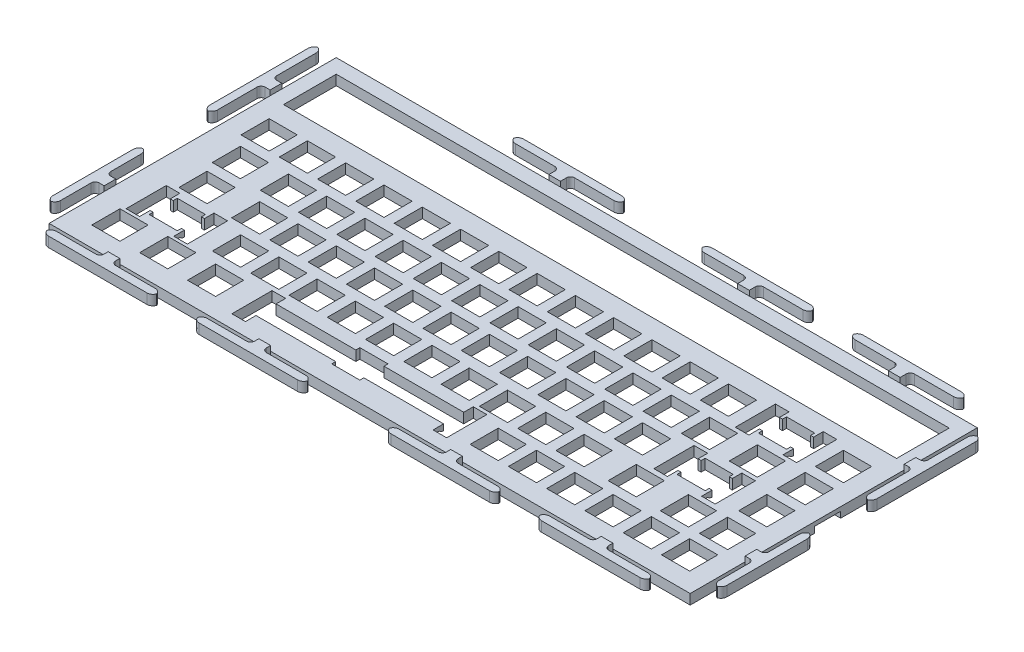
SolidWorks part; units mm, degrees
ref_plane "Front Plane" through (0, 0, 0) normal (0, 0, 1) x (1, 0, 0)
ref_plane "Top Plane" through (0, 0, 0) normal (0, 1, 0) x (1, 0, 0)
ref_plane "Right Plane" through (0, 0, 0) normal (1, 0, 0) x (0, 0, -1)
sketch "Sketch1" plane through (0, 0, 0) normal (0, 1, 0) x (1, 0, 0)
  line L2 (-75.7545, 37.9956) -> (-61.7545, 37.9956)
  line L3 (-94.8265, 37.9956) -> (-80.8265, 37.9956)
  line L4 (-94.8265, 37.9956) -> (-94.8265, 51.9956)
  line L5 (-94.8265, 51.9956) -> (-80.8265, 51.9956)
  line L6 (-80.8265, 37.9956) -> (-80.8265, 51.9956)
  line L7 (-75.7545, 37.9956) -> (-75.7545, 51.9956)
  line L8 (-75.7545, 51.9956) -> (-61.7545, 51.9956)
  line L9 (-61.7545, 37.9956) -> (-61.7545, 51.9956)
  line L10 (133.7495, 37.9956) -> (147.7495, 37.9956)
  line L11 (-37.6545, 37.9956) -> (-23.6545, 37.9956)
  line L12 (-56.7045, 37.9956) -> (-42.7045, 37.9956)
  line L13 (-56.7045, 37.9956) -> (-56.7045, 51.9956)
  line L14 (-56.7045, 51.9956) -> (-42.7045, 51.9956)
  line L15 (-42.7045, 37.9956) -> (-42.7045, 51.9956)
  line L16 (-37.6545, 37.9956) -> (-37.6545, 51.9956)
  line L17 (-37.6545, 51.9956) -> (-23.6545, 51.9956)
  line L18 (-23.6545, 37.9956) -> (-23.6545, 51.9956)
  line L19 (133.7495, 37.9956) -> (133.7495, 51.9956)
  line L20 (133.7495, 51.9956) -> (147.7495, 51.9956)
  line L21 (0.4455, 37.9956) -> (14.4455, 37.9956)
  line L22 (-18.6045, 37.9956) -> (-4.6045, 37.9956)
  line L23 (-18.6045, 37.9956) -> (-18.6045, 51.9956)
  line L24 (-18.6045, 51.9956) -> (-4.6045, 51.9956)
  line L25 (-4.6045, 37.9956) -> (-4.6045, 51.9956)
  line L26 (0.4455, 37.9956) -> (0.4455, 51.9956)
  line L27 (0.4455, 51.9956) -> (14.4455, 51.9956)
  line L28 (14.4455, 37.9956) -> (14.4455, 51.9956)
  line L29 (147.7495, 37.9956) -> (147.7495, 51.9956)
  line L30 (38.5455, 37.9956) -> (52.5455, 37.9956)
  line L31 (19.4955, 37.9956) -> (33.4955, 37.9956)
  line L32 (19.4955, 37.9956) -> (19.4955, 51.9956)
  line L33 (19.4955, 51.9956) -> (33.4955, 51.9956)
  line L34 (33.4955, 37.9956) -> (33.4955, 51.9956)
  line L35 (38.5455, 37.9956) -> (38.5455, 51.9956)
  line L36 (38.5455, 51.9956) -> (52.5455, 51.9956)
  line L37 (52.5455, 37.9956) -> (52.5455, 51.9956)
  line L38 (147.7495, 44.9956) -> (154.1495, 44.9956) construction
  line L39 (167.1835, 18.9456) -> (181.1835, 18.9456)
  line L40 (167.1835, 18.9456) -> (167.1835, 32.9456)
  line L41 (76.6455, 37.9956) -> (90.6455, 37.9956)
  line L42 (57.5955, 37.9956) -> (71.5955, 37.9956)
  line L43 (57.5955, 37.9956) -> (57.5955, 51.9956)
  line L44 (57.5955, 51.9956) -> (71.5955, 51.9956)
  line L45 (71.5955, 37.9956) -> (71.5955, 51.9956)
  line L46 (76.6455, 37.9956) -> (76.6455, 51.9956)
  line L47 (76.6455, 51.9956) -> (90.6455, 51.9956)
  line L48 (90.6455, 37.9956) -> (90.6455, 51.9956)
  line L49 (167.1835, 32.9456) -> (181.1835, 32.9456)
  line L50 (114.7225, 37.9956) -> (128.7225, 37.9956)
  line L51 (95.6955, 37.9956) -> (109.6955, 37.9956)
  line L52 (95.6955, 37.9956) -> (95.6955, 51.9956)
  line L53 (95.6955, 51.9956) -> (109.6955, 51.9956)
  line L54 (109.6955, 37.9956) -> (109.6955, 51.9956)
  line L55 (114.7225, 37.9956) -> (114.7225, 51.9956)
  line L56 (114.7225, 51.9956) -> (128.7225, 51.9956)
  line L57 (128.7225, 37.9956) -> (128.7225, 51.9956)
  line L58 (181.1835, 18.9456) -> (181.1835, 32.9456)
  line L59 (157.3735, 25.9456) -> (167.1835, 25.9456) construction
  line L73 (162.3995, 52.2456) -> (176.3995, 52.2456)
  line L75 (176.3995, 38.2456) -> (162.3995, 38.2456)
  line L77 (176.3995, 52.2456) -> (176.3995, 50.2456)
  line L78 (176.3995, 50.2456) -> (177.8995, 50.2456)
  line L79 (177.8995, 50.2456) -> (177.8995, 54.9956)
  line L80 (177.8995, 54.9956) -> (184.6495, 54.9956)
  line L81 (184.6495, 54.9956) -> (184.6495, 34.9956)
  line L82 (184.6495, 34.9956) -> (177.8995, 34.9956)
  line L83 (177.8995, 34.9956) -> (177.8995, 40.2456)
  line L84 (177.8995, 40.2456) -> (176.3995, 40.2456)
  line L85 (176.3995, 40.2456) -> (176.3995, 38.2456)
  line L86 (162.3995, 52.2456) -> (162.3995, 50.2456)
  line L87 (160.8995, 54.9956) -> (160.8995, 50.2456)
  line L88 (160.8995, 50.2456) -> (162.3995, 50.2456)
  line L89 (160.8995, 54.9956) -> (154.1495, 54.9956)
  line L90 (154.1495, 54.9956) -> (154.1495, 34.9956)
  line L91 (154.1495, 34.9956) -> (160.8995, 34.9956)
  line L92 (160.8995, 34.9956) -> (160.8995, 40.2456)
  line L93 (160.8995, 40.2456) -> (162.3995, 40.2456)
  line L94 (162.3995, 40.2456) -> (162.3995, 38.2456)
  line L116 (-47.1265, 18.9456) -> (-33.1265, 18.9456)
  line L117 (-66.1765, 18.9456) -> (-52.1765, 18.9456)
  line L118 (-66.1765, 18.9456) -> (-66.1765, 32.9456)
  line L119 (-66.1765, 32.9456) -> (-52.1765, 32.9456)
  line L120 (-52.1765, 18.9456) -> (-52.1765, 32.9456)
  line L121 (-47.1265, 18.9456) -> (-47.1265, 32.9456)
  line L122 (-47.1265, 32.9456) -> (-33.1265, 32.9456)
  line L123 (-33.1265, 18.9456) -> (-33.1265, 32.9456)
  line L125 (-9.0515, 18.9456) -> (4.9485, 18.9456)
  line L126 (-28.0765, 18.9456) -> (-14.0765, 18.9456)
  line L127 (-28.0765, 18.9456) -> (-28.0765, 32.9456)
  line L128 (-28.0765, 32.9456) -> (-14.0765, 32.9456)
  line L129 (-14.0765, 18.9456) -> (-14.0765, 32.9456)
  line L130 (-9.0515, 18.9456) -> (-9.0515, 32.9456)
  line L131 (-9.0515, 32.9456) -> (4.9485, 32.9456)
  line L132 (4.9485, 18.9456) -> (4.9485, 32.9456)
  line L135 (29.0735, 18.9456) -> (43.0735, 18.9456)
  line L136 (9.9485, 18.9456) -> (23.9485, 18.9456)
  line L137 (9.9485, 18.9456) -> (9.9485, 32.9456)
  line L138 (9.9485, 32.9456) -> (23.9485, 32.9456)
  line L139 (23.9485, 18.9456) -> (23.9485, 32.9456)
  line L140 (29.0735, 18.9456) -> (29.0735, 32.9456)
  line L141 (29.0735, 32.9456) -> (43.0735, 32.9456)
  line L142 (43.0735, 18.9456) -> (43.0735, 32.9456)
  line L144 (67.1485, 18.9456) -> (81.1485, 18.9456)
  line L145 (48.1235, 18.9456) -> (62.1235, 18.9456)
  line L146 (48.1235, 18.9456) -> (48.1235, 32.9456)
  line L147 (48.1235, 32.9456) -> (62.1235, 32.9456)
  line L148 (62.1235, 18.9456) -> (62.1235, 32.9456)
  line L149 (67.1485, 18.9456) -> (67.1485, 32.9456)
  line L150 (67.1485, 32.9456) -> (81.1485, 32.9456)
  line L151 (81.1485, 18.9456) -> (81.1485, 32.9456)
  line L152 (159.9865, 14.1456) -> (173.9865, 14.1456)
  line L153 (-42.3635, -0.1044) -> (-28.3635, -0.1044)
  line L154 (-61.4135, -0.1044) -> (-47.4135, -0.1044)
  line L155 (105.2735, 18.9456) -> (119.2735, 18.9456)
  line L156 (86.2235, 18.9456) -> (100.2235, 18.9456)
  line L157 (86.2235, 18.9456) -> (86.2235, 32.9456)
  line L158 (86.2235, 32.9456) -> (100.2235, 32.9456)
  line L159 (100.2235, 18.9456) -> (100.2235, 32.9456)
  line L160 (105.2735, 18.9456) -> (105.2735, 32.9456)
  line L161 (105.2735, 32.9456) -> (119.2735, 32.9456)
  line L162 (119.2735, 18.9456) -> (119.2735, 32.9456)
  line L163 (-61.4135, -0.1044) -> (-61.4135, 13.8956)
  line L172 (-94.8265, 37.9956) -> (-94.8265, 32.9456) construction
  line L173 (-61.4135, 13.8956) -> (-47.4135, 13.8956)
  line L174 (-47.4135, -0.1044) -> (-47.4135, 13.8956)
  line L175 (-90.0635, 18.9456) -> (-76.0635, 18.9456)
  line L176 (-90.0635, 18.9456) -> (-90.0635, 32.9456)
  line L177 (-90.0635, 32.9456) -> (-76.0635, 32.9456)
  line L178 (-76.0635, 18.9456) -> (-76.0635, 32.9456)
  line L179 (-94.8265, 32.9456) -> (-90.0635, 32.9456) construction
  line L180 (124.3235, 18.9456) -> (138.3235, 18.9456)
  line L185 (124.3235, 18.9456) -> (124.3235, 32.9456)
  line L186 (124.3235, 32.9456) -> (138.3235, 32.9456)
  line L187 (138.3235, 18.9456) -> (138.3235, 32.9456)
  line L188 (-42.3635, -0.1044) -> (-42.3635, 13.8956)
  line L189 (143.3735, 18.9456) -> (157.3735, 18.9456)
  line L190 (143.3735, 18.9456) -> (143.3735, 32.9456)
  line L191 (143.3735, 32.9456) -> (157.3735, 32.9456)
  line L192 (157.3735, 18.9456) -> (157.3735, 32.9456)
  line L193 (-42.3635, 13.8956) -> (-28.3635, 13.8956)
  line L194 (-28.3635, -0.1044) -> (-28.3635, 13.8956)
  line L195 (-4.2635, -0.1044) -> (9.7365, -0.1044)
  line L196 (-23.3135, -0.1044) -> (-9.3135, -0.1044)
  line L197 (-23.3135, -0.1044) -> (-23.3135, 13.8956)
  line L198 (-23.3135, 13.8956) -> (-9.3135, 13.8956)
  line L199 (-9.3135, -0.1044) -> (-9.3135, 13.8956)
  line L200 (-4.2635, -0.1044) -> (-4.2635, 13.8956)
  line L201 (-4.2635, 13.8956) -> (9.7365, 13.8956)
  line L202 (9.7365, -0.1044) -> (9.7365, 13.8956)
  line L203 (33.8365, -0.1044) -> (47.8365, -0.1044)
  line L204 (14.7865, -0.1044) -> (28.7865, -0.1044)
  line L205 (14.7865, -0.1044) -> (14.7865, 13.8956)
  line L206 (14.7865, 13.8956) -> (28.7865, 13.8956)
  line L207 (28.7865, -0.1044) -> (28.7865, 13.8956)
  line L208 (33.8365, -0.1044) -> (33.8365, 13.8956)
  line L209 (33.8365, 13.8956) -> (47.8365, 13.8956)
  line L210 (47.8365, -0.1044) -> (47.8365, 13.8956)
  line L211 (71.9365, -0.1044) -> (85.9365, -0.1044)
  line L212 (52.8865, -0.1044) -> (66.8865, -0.1044)
  line L213 (52.8865, -0.1044) -> (52.8865, 13.8956)
  line L214 (52.8865, 13.8956) -> (66.8865, 13.8956)
  line L215 (66.8865, -0.1044) -> (66.8865, 13.8956)
  line L216 (71.9365, -0.1044) -> (71.9365, 13.8956)
  line L217 (71.9365, 13.8956) -> (85.9365, 13.8956)
  line L218 (85.9365, -0.1044) -> (85.9365, 13.8956)
  line L219 (110.0365, -0.1044) -> (124.0365, -0.1044)
  line L220 (90.9865, -0.1044) -> (104.9865, -0.1044)
  line L221 (90.9865, -0.1044) -> (90.9865, 13.8956)
  line L222 (90.9865, 13.8956) -> (104.9865, 13.8956)
  line L223 (104.9865, -0.1044) -> (104.9865, 13.8956)
  line L224 (110.0365, -0.1044) -> (110.0365, 13.8956)
  line L225 (110.0365, 13.8956) -> (124.0365, 13.8956)
  line L226 (124.0365, -0.1044) -> (124.0365, 13.8956)
  line L227 (-87.6075, -0.1044) -> (-73.6075, -0.1044)
  line L228 (-87.6075, -0.1044) -> (-87.6075, 13.8956)
  line L229 (-87.6075, 13.8956) -> (-73.6075, 13.8956)
  line L230 (-73.6075, -0.1044) -> (-73.6075, 13.8956)
  line L231 (-90.0635, 18.9456) -> (-90.0635, 13.8956) construction
  line L232 (129.0865, -0.1044) -> (143.0865, -0.1044)
  line L233 (129.0865, -0.1044) -> (129.0865, 13.8956)
  line L234 (129.0865, 13.8956) -> (143.0865, 13.8956)
  line L235 (143.0865, -0.1044) -> (143.0865, 13.8956)
  line L240 (-90.0635, 13.8956) -> (-87.6075, 13.8956) construction
  line L241 (173.9865, 0.1456) -> (159.9865, 0.1456)
  line L242 (173.9865, 14.1456) -> (173.9865, 12.1456)
  line L243 (173.9865, 12.1456) -> (175.4865, 12.1456)
  line L244 (175.4865, 12.1456) -> (175.4865, 16.8956)
  line L245 (175.4865, 16.8956) -> (182.2365, 16.8956)
  line L246 (182.2365, 16.8956) -> (182.2365, -3.1044)
  line L247 (182.2365, -3.1044) -> (175.4865, -3.1044)
  line L248 (175.4865, -3.1044) -> (175.4865, 2.1456)
  line L249 (175.4865, 2.1456) -> (173.9865, 2.1456)
  line L250 (173.9865, 2.1456) -> (173.9865, 0.1456)
  line L251 (159.9865, 14.1456) -> (159.9865, 12.1456)
  line L252 (158.4865, 16.8956) -> (158.4865, 12.1456)
  line L253 (158.4865, 12.1456) -> (159.9865, 12.1456)
  line L254 (158.4865, 16.8956) -> (151.7365, 16.8956)
  line L255 (151.7365, 16.8956) -> (151.7365, -3.1044)
  line L256 (151.7365, -3.1044) -> (158.4865, -3.1044)
  line L257 (158.4865, -3.1044) -> (158.4865, 2.1456)
  line L258 (158.4865, 2.1456) -> (159.9865, 2.1456)
  line L259 (159.9865, 2.1456) -> (159.9865, 0.1456)
  line L260 (143.0865, 12.1456) -> (151.7365, 12.1456) construction
  line L262 (-32.8385, -19.1544) -> (-18.8385, -19.1544)
  line L263 (-51.8885, -19.1544) -> (-37.8885, -19.1544)
  line L264 (-51.8885, -19.1544) -> (-51.8885, -5.1544)
  line L265 (-51.8885, -5.1544) -> (-37.8885, -5.1544)
  line L266 (-37.8885, -19.1544) -> (-37.8885, -5.1544)
  line L267 (-32.8385, -19.1544) -> (-32.8385, -5.1544)
  line L268 (-32.8385, -5.1544) -> (-18.8385, -5.1544)
  line L269 (-18.8385, -19.1544) -> (-18.8385, -5.1544)
  line L270 (5.2615, -19.1544) -> (19.2615, -19.1544)
  line L271 (-13.7885, -19.1544) -> (0.2115, -19.1544)
  line L272 (-13.7885, -19.1544) -> (-13.7885, -5.1544)
  line L273 (-13.7885, -5.1544) -> (0.2115, -5.1544)
  line L274 (0.2115, -19.1544) -> (0.2115, -5.1544)
  line L275 (5.2615, -19.1544) -> (5.2615, -5.1544)
  line L276 (5.2615, -5.1544) -> (19.2615, -5.1544)
  line L277 (19.2615, -19.1544) -> (19.2615, -5.1544)
  line L278 (43.3615, -19.1544) -> (57.3615, -19.1544)
  line L279 (24.3115, -19.1544) -> (38.3115, -19.1544)
  line L280 (24.3115, -19.1544) -> (24.3115, -5.1544)
  line L281 (24.3115, -5.1544) -> (38.3115, -5.1544)
  line L282 (38.3115, -19.1544) -> (38.3115, -5.1544)
  line L283 (43.3615, -19.1544) -> (43.3615, -5.1544)
  line L284 (43.3615, -5.1544) -> (57.3615, -5.1544)
  line L285 (57.3615, -19.1544) -> (57.3615, -5.1544)
  line L286 (81.4615, -19.6544) -> (95.4615, -19.6544)
  line L287 (62.4115, -19.6544) -> (76.4115, -19.6544)
  line L288 (62.4115, -19.6544) -> (62.4115, -5.6544)
  line L289 (62.4115, -5.6544) -> (76.4115, -5.6544)
  line L290 (76.4115, -19.6544) -> (76.4115, -5.6544)
  line L291 (81.4615, -19.6544) -> (81.4615, -5.6544)
  line L292 (81.4615, -5.6544) -> (95.4615, -5.6544)
  line L293 (95.4615, -19.6544) -> (95.4615, -5.6544)
  line L294 (119.5615, -19.6544) -> (133.5615, -19.6544)
  line L295 (100.5115, -19.6544) -> (114.5115, -19.6544)
  line L296 (100.5115, -19.6544) -> (100.5115, -5.6544)
  line L297 (100.5115, -5.6544) -> (114.5115, -5.6544)
  line L298 (114.5115, -19.6544) -> (114.5115, -5.6544)
  line L299 (119.5615, -19.6544) -> (119.5615, -5.6544)
  line L300 (119.5615, -5.6544) -> (133.5615, -5.6544)
  line L301 (133.5615, -19.6544) -> (133.5615, -5.6544)
  line L306 (-83.3445, -5.1544) -> (-69.3445, -5.1544)
  line L307 (145.5235, -19.6544) -> (159.5235, -19.6544)
  line L308 (145.5235, -19.6544) -> (145.5235, -5.6544)
  line L309 (145.5235, -5.6544) -> (159.5235, -5.6544)
  line L310 (159.5235, -19.6544) -> (159.5235, -5.6544)
  line L311 (-69.3445, -19.1544) -> (-83.3445, -19.1544)
  line L331 (171.4855, -19.6544) -> (185.4855, -19.6544)
  line L332 (171.4855, -19.6544) -> (171.4855, -5.6544)
  line L333 (171.4855, -5.6544) -> (185.4855, -5.6544)
  line L334 (185.4855, -19.6544) -> (185.4855, -5.6544)
  line L335 (159.5235, -12.6544) -> (171.4855, -12.6544) construction
  line L336 (-61.4135, -0.1044) -> (-61.4135, -5.1544) construction
  line L337 (-61.4135, -5.1544) -> (-51.8885, -5.1544) construction
  line L338 (-104.4215, 94.9896) -> (-117.5239, 94.9896) construction
  line L339 (-97.2765, 61.6456) -> (207.7235, 61.6456)
  line L340 (190.9955, 18.9456) -> (204.9955, 18.9456)
  line L341 (190.9955, 18.9456) -> (190.9955, 32.9456)
  line L342 (190.9955, 32.9456) -> (204.9955, 32.9456)
  line L343 (204.9955, 18.9456) -> (204.9955, 32.9456)
  line L344 (181.1835, 25.9456) -> (190.9955, 25.9456) construction
  line L345 (190.9745, 37.9956) -> (204.9745, 37.9956)
  line L346 (190.9745, 37.9956) -> (190.9745, 51.9956)
  line L347 (190.9745, 51.9956) -> (204.9745, 51.9956)
  line L348 (204.9745, 37.9956) -> (204.9745, 51.9956)
  line L349 (184.6495, 44.9956) -> (190.9745, 44.9956) construction
  line L350 (190.9425, -0.1044) -> (204.9425, -0.1044)
  line L351 (190.9425, -0.1044) -> (190.9425, 13.8956)
  line L352 (190.9425, 13.8956) -> (204.9425, 13.8956)
  line L353 (204.9425, -0.1044) -> (204.9425, 13.8956)
  line L354 (182.2365, 6.8956) -> (190.9425, 6.8956) construction
  line L355 (190.9855, -19.6544) -> (204.9855, -19.6544)
  line L356 (190.9855, -19.6544) -> (190.9855, -5.6544)
  line L357 (190.9855, -5.6544) -> (204.9855, -5.6544)
  line L358 (204.9855, -19.6544) -> (204.9855, -5.6544)
  line L359 (185.4855, -12.6544) -> (190.9855, -12.6544) construction
  line L360 (-69.3445, -5.1544) -> (-69.3445, -7.1544)
  line L361 (-69.3445, -7.1544) -> (-67.8445, -7.1544)
  line L362 (-67.8445, -7.1544) -> (-67.8445, -2.4044)
  line L363 (-67.8445, -2.4044) -> (-61.0945, -2.4044)
  line L364 (-61.0945, -2.4044) -> (-61.0945, -22.4044)
  line L365 (-61.0945, -22.4044) -> (-67.8445, -22.4044)
  line L366 (-67.8445, -22.4044) -> (-67.8445, -17.1544)
  line L367 (-67.8445, -17.1544) -> (-69.3445, -17.1544)
  line L368 (-69.3445, -17.1544) -> (-69.3445, -19.1544)
  line L369 (-83.3445, -5.1544) -> (-83.3445, -7.1544)
  line L370 (-84.8445, -2.4044) -> (-84.8445, -7.1544)
  line L371 (-84.8445, -7.1544) -> (-83.3445, -7.1544)
  line L372 (-84.8445, -2.4044) -> (-91.5945, -2.4044)
  line L373 (-91.5945, -2.4044) -> (-91.5945, -22.4044)
  line L374 (-91.5945, -22.4044) -> (-84.8445, -22.4044)
  line L375 (-84.8445, -22.4044) -> (-84.8445, -17.1544)
  line L376 (-84.8445, -17.1544) -> (-83.3445, -17.1544)
  line L377 (-83.3445, -17.1544) -> (-83.3445, -19.1544)
  line L378 (-93.0945, -37.9544) -> (-79.0945, -37.9544)
  line L379 (-93.0945, -37.9544) -> (-93.0945, -23.9544)
  line L380 (-93.0945, -23.9544) -> (-79.0945, -23.9544)
  line L381 (-79.0945, -37.9544) -> (-79.0945, -23.9544)
  line L382 (-69.2945, -37.9544) -> (-55.2945, -37.9544)
  line L383 (-69.2945, -37.9544) -> (-69.2945, -23.9544)
  line L384 (-69.2945, -23.9544) -> (-55.2945, -23.9544)
  line L385 (-55.2945, -37.9544) -> (-55.2945, -23.9544)
  line L390 (-45.4945, -37.9544) -> (-31.4945, -37.9544)
  line L391 (-45.4945, -37.9544) -> (-45.4945, -23.9544)
  line L392 (-45.4945, -23.9544) -> (-31.4945, -23.9544)
  line L393 (-31.4945, -37.9544) -> (-31.4945, -23.9544)
  line L394 (-55.2945, -23.9544) -> (-45.4945, -23.9544) construction
  line L395 (26.4395, -24.1144) -> (40.4395, -24.1144)
  line L396 (40.4395, -38.1144) -> (26.4395, -38.1144)
  line L397 (40.4395, -24.1144) -> (40.4395, -26.1144)
  line L398 (40.4395, -26.1144) -> (80.1235, -26.1144)
  line L399 (80.1235, -26.1144) -> (80.1235, -21.3644)
  line L400 (80.1235, -21.3644) -> (86.8735, -21.3644)
  line L401 (86.8735, -21.3644) -> (86.8735, -41.3644)
  line L402 (86.8735, -41.3644) -> (80.1235, -41.3644)
  line L403 (80.1235, -41.3644) -> (80.1235, -36.1144)
  line L404 (80.1235, -36.1144) -> (40.4395, -36.1144)
  line L405 (40.4395, -36.1144) -> (40.4395, -38.1144)
  line L406 (26.4395, -24.1144) -> (26.4395, -26.1144)
  line L407 (-13.2445, -21.3644) -> (-13.2445, -26.1144)
  line L408 (-13.2445, -26.1144) -> (26.4395, -26.1144)
  line L409 (-13.2445, -21.3644) -> (-19.9945, -21.3644)
  line L410 (-19.9945, -21.3644) -> (-19.9945, -41.3644)
  line L411 (-19.9945, -41.3644) -> (-13.2445, -41.3644)
  line L412 (-13.2445, -41.3644) -> (-13.2445, -36.1144)
  line L413 (-13.2445, -36.1144) -> (26.4395, -36.1144)
  line L414 (26.4395, -36.1144) -> (26.4395, -38.1144)
  line L415 (95.5435, -38.3644) -> (109.5435, -38.3644)
  line L416 (95.5435, -38.3644) -> (95.5435, -24.3644)
  line L417 (95.5435, -24.3644) -> (109.5435, -24.3644)
  line L418 (109.5435, -38.3644) -> (109.5435, -24.3644)
  line L419 (86.8735, -31.3644) -> (95.5435, -31.3644) construction
  line L420 (114.5935, -38.3644) -> (128.5935, -38.3644)
  line L421 (114.5935, -38.3644) -> (114.5935, -24.3644)
  line L422 (114.5935, -24.3644) -> (128.5935, -24.3644)
  line L423 (128.5935, -38.3644) -> (128.5935, -24.3644)
  line L424 (114.5935, -31.3644) -> (109.5435, -31.3644) construction
  line L425 (133.6435, -38.3644) -> (147.6435, -38.3644)
  line L426 (133.6435, -38.3644) -> (133.6435, -24.3644)
  line L427 (133.6435, -24.3644) -> (147.6435, -24.3644)
  line L428 (147.6435, -38.3644) -> (147.6435, -24.3644)
  line L429 (152.6935, -38.3644) -> (166.6935, -38.3644)
  line L430 (152.6935, -38.3644) -> (152.6935, -24.3644)
  line L431 (152.6935, -24.3644) -> (166.6935, -24.3644)
  line L432 (166.6935, -38.3644) -> (166.6935, -24.3644)
  line L433 (171.7435, -38.3644) -> (185.7435, -38.3644)
  line L434 (171.7435, -38.3644) -> (171.7435, -24.3644)
  line L435 (171.7435, -24.3644) -> (185.7435, -24.3644)
  line L436 (185.7435, -38.3644) -> (185.7435, -24.3644)
  line L437 (190.7935, -38.3644) -> (204.7935, -38.3644)
  line L438 (190.7935, -38.3644) -> (190.7935, -24.3644)
  line L439 (190.7935, -24.3644) -> (204.7935, -24.3644)
  line L440 (204.7935, -38.3644) -> (204.7935, -24.3644)
  line L441 (-97.2765, 61.6456) -> (-97.2765, 87.8456)
  line L442 (-97.2765, 87.8456) -> (207.7235, 87.8456)
  line L443 (207.7235, 61.6456) -> (207.7235, 87.8456)
  line L444 (-104.4215, 94.9896) -> (214.5785, 94.9896)
  line L445 (-104.4215, 94.9896) -> (-104.4215, -47.8854)
  line L446 (-104.4215, -47.8854) -> (214.5785, -47.8854)
  line L447 (214.5785, 94.9896) -> (214.5785, -47.8854)
  line L448 (-117.5239, 94.9896) -> (-117.5239, 25.8096) construction
  line L449 (-104.4215, -47.8854) -> (-117.5239, -47.8854) construction
  line L450 (-117.5239, -47.8854) -> (-117.5239, 14.6046) construction
  line L451 (-150.5498, 25.8096) -> (-98.6233, 25.8096) construction
  line L452 (-150.5498, 14.6046) -> (-97.2765, 14.6046) construction
  line L453 (-104.4215, 94.9896) -> (-104.4215, 60.3996) construction
  point P115 (128.7225, 44.9956)
  point P116 (154.1495, 44.9956)
  dimension "D1" = 14
  dimension "D2" = 20
  dimension "D3" = 4.75
  dimension "D4" = 6.75
  dimension "D5" = 1.5
  dimension "D6" = 2
  dimension "D13" = 14
  dimension "D14" = 14
  dimension "D15" = 5.072
  dimension "D16" = 14
  dimension "D17" = 5.05
  dimension "D18" = 5.05
  dimension "D19" = 14
  dimension "D20" = 4.763
  dimension "D21" = 5.05
  dimension "D22" = 9.887
  dimension "D23" = 26.2
  dimension "D24" = 14
  dimension "D25" = 14
  dimension "D26" = 5.05
  dimension "D27" = 5.05
  dimension "D28" = 5.05
  dimension "D29" = 5.05
  dimension "D30" = 5.05
  dimension "D31" = 5.05
  dimension "D32" = 5.05
  dimension "D33" = 5.05
  dimension "D34" = 5.05
  dimension "D35" = 5.027
  dimension "D36" = 5.05
  dimension "D37" = 5.05
  dimension "D38" = 5.025
  dimension "D39" = 5
  dimension "D40" = 5.125
  dimension "D41" = 5.05
  dimension "D42" = 5.025
  dimension "D43" = 5.075
  dimension "D44" = 5.05
  dimension "D45" = 5.05
  dimension "D46" = 5.027
  dimension "D47" = 14.65
  dimension "D48" = 14
  dimension "D49" = 9.81
  dimension "D50" = 12.194
  dimension "D51" = 5.05
  dimension "D52" = 5.05
  dimension "D53" = 5.05
  dimension "D54" = 5.05
  dimension "D55" = 5.05
  dimension "D56" = 5.05
  dimension "D57" = 5.05
  dimension "D58" = 5.05
  dimension "D59" = 5.05
  dimension "D60" = 5.05
  dimension "D61" = 14
  dimension "D62" = 20
  dimension "D63" = 5.05
  dimension "D64" = 2.456
  dimension "D65" = 4.75
  dimension "D66" = 6.75
  dimension "D67" = 1.5
  dimension "D68" = 2
  dimension "D69" = 16.9
  dimension "D70" = 14
  dimension "D71" = 5.05
  dimension "D72" = 5.05
  dimension "D73" = 5.05
  dimension "D74" = 5.05
  dimension "D75" = 5.05
  dimension "D76" = 5.05
  dimension "D77" = 5.05
  dimension "D78" = 5.05
  dimension "D79" = 5.05
  dimension "D80" = 11.962
  dimension "D81" = 20
  dimension "D82" = 14
  dimension "D83" = 11.962
  dimension "D84" = 14
  dimension "D85" = 14
  dimension "D86" = 9.812
  dimension "D87" = 14
  dimension "D88" = 14.575
  dimension "D89" = 4.75
  dimension "D90" = 14
  dimension "D91" = 6.75
  dimension "D92" = 14
  dimension "D93" = 16.956
  dimension "D94" = 14
  dimension "D95" = 5.5
  dimension "D96" = 5.05
  dimension "D97" = 5.05
  dimension "D98" = 9.525
  dimension "D99" = 1.5
  dimension "D100" = 2
  dimension "D101" = 5.05
  dimension "D102" = 9.206
  dimension "D103" = 5.05
  dimension "D104" = 14
  dimension "D105" = 14
  dimension "D106" = 14
  dimension "D107" = 14
  dimension "D108" = 1.5
  dimension "D109" = 9.8
  dimension "D110" = 5.05
  dimension "D111" = 9.8
  dimension "D112" = 5.05
  dimension "D113" = 5.05
  dimension "D114" = 14
  dimension "D115" = 14
  dimension "D116" = 20
  dimension "D117" = 4.75
  dimension "D118" = 6.75
  dimension "D119" = 39.684
  dimension "D120" = 2
  dimension "D121" = 5.05
  dimension "D122" = 11.5
  dimension "D123" = 14
  dimension "D124" = 8.67
  dimension "D125" = 5.25
  dimension "D126" = 14
  dimension "D127" = 5.05
  dimension "D128" = 14
  dimension "D129" = 14
  dimension "D130" = 14
  dimension "D131" = 14
  dimension "D132" = 5.05
  dimension "D133" = 5.05
  dimension "D134" = 5.05
  dimension "D135" = 5.05
  dimension "D136" = 4.8
  dimension "D137" = 5.25
  dimension "D138" = 5.25
  dimension "D139" = 5.25
  dimension "D140" = 305
  dimension "D141" = 9.65
  dimension "D142" = 142.875
  dimension "D143" = 319
  dimension "D144" = 7.144
  dimension "D145" = 7.145
  dimension "D146" = 2.45
  dimension "D147" = 69.18
  dimension "D148" = 62.49
extrude "Boss-Extrude2" add sketch "Sketch1" along normal mid plane 5
sketch "Sketch2" plane through (0, 2.5, 0) normal (0, 1, 0) x (1, 0, 0)
  line L0 (-104.4215, 25.7896) -> (-104.4215, 14.6146) construction
  line L1 (-104.4215, -47.8854) -> (-104.4215, -20.4854) construction
  line L2 (-104.4215, 94.9896) -> (-104.4215, -47.8854) construction
  line L14 (-107.4215, 20.2021) -> (-104.4215, 20.2021) construction
  line L16 (-107.4215, 31.2421) -> (-107.4215, 9.1621) construction
  line L25 (214.5785, 64.3896) -> (214.5785, 58.5896)
  line L26 (55.1185, 125.3194) -> (55.1185, -78.0627) construction
  line L44 (214.5785, 58.5896) -> (218.6785, 58.5896)
  line L45 (218.6785, 58.5896) -> (218.6785, 33.9896)
  line L46 (218.6785, 33.9896) -> (222.6785, 33.9896)
  line L47 (222.6785, 33.9896) -> (222.6785, 88.9896)
  line L48 (55.0785, 94.9896) -> (55.0785, -47.8854) construction
  line L49 (214.5785, 94.9896) -> (-104.4215, 94.9896) construction
  line L50 (-104.4215, -47.8854) -> (214.5785, -47.8854) construction
  line L51 (55.1185, 23.6283) -> (270.1989, 23.6283) construction
  line L52 (55.1185, 23.6283) -> (-168.679, 23.6283) construction
  line L55 (45.7235, 94.9896) -> (56.8285, 94.9896) construction
  line L56 (51.276, 94.9896) -> (51.276, 98.9896) construction
  line L57 (40.236, 98.9896) -> (62.316, 98.9896) construction
  line L74 (222.6785, 88.9896) -> (218.6785, 88.9896)
  line L75 (214.5785, 94.9896) -> (176.1966, 94.9896) construction
  line L124 (55.0785, -47.8854) -> (95.4285, -47.8854) construction
  line L125 (-104.4215, 67.8896) -> (-104.4215, 62.0896)
  line L127 (45.7225, -47.8854) -> (56.8335, -47.8854) construction
  line L128 (51.278, -47.8854) -> (51.278, -52.8854) construction
  line L129 (40.276, -52.8854) -> (62.356, -52.8854) construction
  line L134 (-104.4215, 62.0896) -> (-108.9215, 62.0896)
  line L135 (-108.9215, 62.0896) -> (-108.9215, 37.4896)
  line L136 (-108.9215, 37.4896) -> (-112.9215, 37.4896)
  line L137 (-112.9215, 37.4896) -> (-112.9215, 92.4896)
  line L138 (-112.9215, 92.4896) -> (-108.9215, 92.4896)
  line L139 (-108.9215, 92.4896) -> (-108.9215, 67.8896)
  line L140 (-108.9215, 67.8896) -> (-104.4215, 67.8896)
  line L141 (-104.4215, 94.9896) -> (-104.4215, 67.8896) construction
  line L142 (-104.4215, -14.6854) -> (-104.4215, -20.4854)
  line L143 (-104.4215, -20.4854) -> (-108.9215, -20.4854)
  line L144 (-108.9215, -20.4854) -> (-108.9215, -40.5854)
  line L145 (-108.9215, -40.5854) -> (-112.9215, -40.5854)
  line L146 (-112.9215, -40.5854) -> (-112.9215, 5.4146)
  line L147 (-112.9215, 5.4146) -> (-108.9215, 5.4146)
  line L148 (-108.9215, 5.4146) -> (-108.9215, -14.6854)
  line L149 (-108.9215, -14.6854) -> (-104.4215, -14.6854)
  line L150 (1.3585, 94.9896) -> (7.1585, 94.9896)
  line L151 (7.1585, 94.9896) -> (7.1585, 99.9896)
  line L152 (7.1585, 99.9896) -> (31.7585, 99.9896)
  line L153 (31.7585, 99.9896) -> (31.7585, 103.9896)
  line L154 (31.7585, 103.9896) -> (-23.2415, 103.9896)
  line L155 (-23.2415, 103.9896) -> (-23.2415, 99.9896)
  line L156 (-23.2415, 99.9896) -> (1.3585, 99.9896)
  line L157 (1.3585, 99.9896) -> (1.3585, 94.9896)
  line L158 (55.0785, 94.9896) -> (7.1585, 94.9896) construction
  line L166 (-75.0215, -47.8854) -> (-69.2215, -47.8854)
  line L167 (-69.2215, -47.8854) -> (-69.2215, -51.9854)
  line L168 (-69.2215, -51.9854) -> (-44.6215, -51.9854)
  line L169 (-44.6215, -51.9854) -> (-44.6215, -55.9854)
  line L170 (-44.6215, -55.9854) -> (-99.6215, -55.9854)
  line L171 (-99.6215, -55.9854) -> (-99.6215, -51.9854)
  line L172 (-99.6215, -51.9854) -> (-75.0215, -51.9854)
  line L173 (-75.0215, -51.9854) -> (-75.0215, -47.8854)
  line L174 (-0.0215, -47.8854) -> (5.7785, -47.8854)
  line L175 (5.7785, -47.8854) -> (5.7785, -51.9854)
  line L176 (5.7785, -51.9854) -> (30.3785, -51.9854)
  line L177 (30.3785, -51.9854) -> (30.3785, -55.9854)
  line L178 (30.3785, -55.9854) -> (-24.6215, -55.9854)
  line L179 (-24.6215, -55.9854) -> (-24.6215, -51.9854)
  line L180 (-24.6215, -51.9854) -> (-0.0215, -51.9854)
  line L181 (-0.0215, -51.9854) -> (-0.0215, -47.8854)
  line L182 (-104.4215, -47.8854) -> (-75.0215, -47.8854) construction
  line L183 (95.4285, -47.8854) -> (101.2285, -47.8854)
  line L184 (101.2285, -47.8854) -> (101.2285, -51.9854)
  line L185 (101.2285, -51.9854) -> (125.8285, -51.9854)
  line L186 (125.8285, -51.9854) -> (125.8285, -55.9854)
  line L187 (125.8285, -55.9854) -> (70.8285, -55.9854)
  line L188 (70.8285, -55.9854) -> (70.8285, -51.9854)
  line L189 (70.8285, -51.9854) -> (95.4285, -51.9854)
  line L190 (95.4285, -51.9854) -> (95.4285, -47.8854)
  line L191 (170.3285, -47.8854) -> (176.1285, -47.8854)
  line L192 (176.1285, -47.8854) -> (176.1285, -51.9854)
  line L193 (176.1285, -51.9854) -> (200.7285, -51.9854)
  line L194 (200.7285, -51.9854) -> (200.7285, -55.9854)
  line L195 (200.7285, -55.9854) -> (145.7285, -55.9854)
  line L196 (145.7285, -55.9854) -> (145.7285, -51.9854)
  line L197 (145.7285, -51.9854) -> (170.3285, -51.9854)
  line L198 (170.3285, -51.9854) -> (170.3285, -47.8854)
  line L199 (55.0785, -47.8854) -> (5.7785, -47.8854) construction
  line L200 (95.3145, 94.9896) -> (101.1145, 94.9896)
  line L201 (101.1145, 94.9896) -> (101.1145, 99.9896)
  line L202 (101.1145, 99.9896) -> (125.7145, 99.9896)
  line L203 (125.7145, 99.9896) -> (125.7145, 103.9896)
  line L204 (125.7145, 103.9896) -> (70.7145, 103.9896)
  line L205 (70.7145, 103.9896) -> (70.7145, 99.9896)
  line L206 (70.7145, 99.9896) -> (95.3145, 99.9896)
  line L207 (95.3145, 99.9896) -> (95.3145, 94.9896)
  line L208 (170.3966, 94.9896) -> (176.1966, 94.9896)
  line L209 (176.1966, 94.9896) -> (176.1966, 99.9896)
  line L210 (176.1966, 99.9896) -> (200.7966, 99.9896)
  line L211 (200.7966, 99.9896) -> (200.7966, 103.9896)
  line L212 (200.7966, 103.9896) -> (145.7966, 103.9896)
  line L213 (145.7966, 103.9896) -> (145.7966, 99.9896)
  line L214 (145.7966, 99.9896) -> (170.3966, 99.9896)
  line L215 (170.3966, 99.9896) -> (170.3966, 94.9896)
  line L216 (214.5785, -47.8854) -> (176.1285, -47.8854) construction
  line L217 (218.6785, 88.9896) -> (218.6785, 64.3896)
  line L218 (218.6785, 64.3896) -> (214.5785, 64.3896)
  line L219 (214.5785, -14.7854) -> (214.5785, -20.5854)
  line L220 (214.5785, -20.5854) -> (218.6785, -20.5854)
  line L221 (218.6785, -20.5854) -> (218.6785, -40.6854)
  line L222 (218.6785, -40.6854) -> (222.6785, -40.6854)
  line L223 (222.6785, -40.6854) -> (222.6785, 5.3146)
  line L224 (222.6785, 5.3146) -> (218.6785, 5.3146)
  line L225 (218.6785, 5.3146) -> (218.6785, -14.7854)
  line L226 (218.6785, -14.7854) -> (214.5785, -14.7854)
  line L227 (214.5785, 94.9896) -> (214.5785, 64.3896) construction
  line L228 (214.5785, -47.8854) -> (214.5785, 94.9896) construction
  line L229 (214.5785, -47.8854) -> (214.5785, -20.5854) construction
  point P28 (-104.4215, 20.2021)
  point P84 (51.276, 98.9896)
  dimension "D4" = 5.8
  dimension "D5" = 4.5
  dimension "D6" = 55
  dimension "D7" = 22.08
  dimension "D8" = 4
  dimension "D9" = 5.8
  dimension "D10" = 4.5
  dimension "D11" = 4
  dimension "D12" = 46
  dimension "D13" = 27.1
  dimension "D14" = 5.8
  dimension "D15" = 4.1
  dimension "D16" = 4
  dimension "D17" = 27.4
  dimension "D18" = 47.92
  dimension "D19" = 4
  dimension "D20" = 22.08
  dimension "D21" = 40.196
  dimension "D22" = 55
  dimension "D23" = 5.8
  dimension "D24" = 4
  dimension "D25" = 46
  dimension "D26" = 30.6
  dimension "D27" = 27.3
  dimension "D29" = 4.1
  dimension "D31" = 38.45
  dimension "D32" = 5.8
  dimension "D33" = 5
  dimension "D34" = 22.08
  dimension "D35" = 5.8
  dimension "D36" = 5
  dimension "D37" = 4
  dimension "D38" = 55
  dimension "D39" = 40.35
  dimension "D40" = 5.8
  dimension "D41" = 4
  dimension "D42" = 55
  dimension "D43" = 4
  dimension "D44" = 55
  dimension "D45" = 4.1
  dimension "D46" = 4.1
  dimension "D47" = 29.4
  dimension "D48" = 5.8
  dimension "D49" = 4
  dimension "D50" = 55
  dimension "D51" = 4.1
  dimension "D52" = 5.8
  dimension "D53" = 4
  dimension "D54" = 55
  dimension "D55" = 4.1
  dimension "D56" = 49.3
  dimension "D57" = 5
  dimension "D58" = 55
  dimension "D59" = 5
  dimension "D60" = 55
extrude "Boss-Extrude3" add sketch "Sketch2" along normal mid plane 5
sketch "Sketch3" plane through (0, 2.5, 0) normal (0, 1, 0) x (1, 0, 0)
  line L0 (208.0785, 94.9896) -> (208.0785, 26.9896) construction
  line L1 (214.5785, 94.9896) -> (176.1966, 94.9896) construction
  line L2 (208.0785, 26.9896) -> (208.0785, 13.9896) construction
  line L3 (214.5785, -14.7854) -> (214.5785, 58.5896) construction
  line L4 (208.0785, 26.9896) -> (208.0785, 13.9896)
  line L5 (208.0785, 13.9896) -> (214.5785, 13.9896)
  line L6 (214.5785, 13.9896) -> (214.5785, 26.9896)
  line L7 (214.5785, 26.9896) -> (208.0785, 26.9896)
  line L8 (58.5785, 89.4896) -> (214.5785, 89.4896) construction
  line L9 (214.5785, 64.3896) -> (214.5785, 94.9896) construction
  line L10 (95.3145, 94.9896) -> (7.1585, 94.9896) construction
  line L11 (58.5785, 89.4896) -> (46.5792, 89.4896)
  line L12 (46.5792, 89.4896) -> (46.5792, 94.9896)
  line L13 (46.5792, 94.9896) -> (58.5785, 94.9896)
  line L14 (58.5785, 94.9896) -> (58.5785, 89.4896)
  line L15 (-97.4215, 94.9896) -> (-97.4215, 26.9896) construction
  line L16 (1.3585, 94.9896) -> (-104.4215, 94.9896) construction
  line L17 (-97.4215, 26.9896) -> (-97.4215, 13.9896) construction
  line L18 (-104.4215, 62.0896) -> (-104.4215, -14.6854) construction
  line L19 (-97.4215, 26.9896) -> (-104.4215, 26.9896)
  line L20 (-104.4215, 26.9896) -> (-104.4215, 13.9896)
  line L21 (-104.4215, 13.9896) -> (-97.4215, 13.9896)
  line L22 (-97.4215, 13.9896) -> (-97.4215, 26.9896)
  dimension "D1" = 68
  dimension "D2" = 13
  dimension "D3" = 6.5
  dimension "D4" = 156
  dimension "D5" = 5.5
  dimension "D6" = 180
  dimension "D7" = 7
extrude "Cut-Extrude1" cut sketch "Sketch3" against normal through all
sketch "Sketch4" plane through (175.4865, 0, 0) normal (1, 0, 0) x (0, 0, -1)
  line L0 (-3.1044, -2.5) -> (-3.1044, 0.5)
  line L8 (-3.1044, 0.5) -> (-0.1044, 0.5)
  line L9 (-0.1044, 0.5) -> (-0.1044, -0.5)
  line L10 (-0.1044, -0.5) -> (2.1456, -0.5)
  line L11 (2.1456, -0.5) -> (2.1456, -2.5)
  line L12 (2.1456, -2.5) -> (-3.1044, -2.5)
  dimension "D1" = 3
  dimension "D2" = 3
  dimension "D3" = 2
extrude "Cut-Extrude2" cut sketch "Sketch4" against normal blind 18
sketch "Sketch6" plane through (177.8995, 0, 0) normal (1, 0, 0) x (0, 0, -1)
  line L8 (34.9956, -2.5) -> (34.9956, 0.5)
  line L9 (34.9956, 2.5) -> (34.9956, -2.5) construction
  line L11 (34.9956, 0.5) -> (37.9956, 0.5)
  line L12 (37.9956, 0.5) -> (37.9956, -0.5)
  line L13 (37.9956, -0.5) -> (40.2456, -0.5)
  line L14 (40.2456, 2.5) -> (40.2456, -2.5) construction
  line L15 (40.2456, -0.5) -> (40.2456, -2.5)
  line L16 (40.2456, -2.5) -> (34.9956, -2.5)
  dimension "D1" = 3
  dimension "D2" = 3
  dimension "D3" = 2
extrude "Cut-Extrude3" cut sketch "Sketch6" against normal blind 18
sketch "Sketch7" plane through (-67.8445, 0, 0) normal (1, 0, 0) x (0, 0, -1)
  line L12 (-22.4044, -2.5) -> (-22.4044, 0.5)
  line L13 (-22.4044, 0.5) -> (-19.4044, 0.5)
  line L14 (-19.4044, 0.5) -> (-19.4044, -0.5)
  line L15 (-19.4044, -0.5) -> (-17.1544, -0.5)
  line L16 (-17.1544, -0.5) -> (-17.1544, -2.5)
  line L17 (-17.1544, -2.5) -> (-22.4044, -2.5)
  dimension "D4" = 3
  dimension "D5" = 3
  dimension "D6" = 2
extrude "Cut-Extrude4" cut sketch "Sketch7" against normal blind 18
sketch "Sketch8" plane through (80.1235, 0, 0) normal (1, 0, 0) x (0, 0, -1)
  line L6 (-41.3644, -2.5) -> (-41.3644, 0.5)
  line L7 (-41.3644, 0.5) -> (-38.3644, 0.5)
  line L8 (-38.3644, 0.5) -> (-38.3644, -0.5)
  line L9 (-38.3644, -0.5) -> (-36.1144, -0.5)
  line L10 (-36.1144, -0.5) -> (-36.1144, -2.5)
  line L11 (-36.1144, -2.5) -> (-41.3644, -2.5)
  dimension "D1" = 3
  dimension "D2" = 3
  dimension "D3" = 2
extrude "Cut-Extrude5" cut sketch "Sketch8" against normal blind 95
sketch "Sketch9" plane through (175.4865, 0, 0) normal (1, 0, 0) x (0, 0, -1)
fillet "Fillet1" radius 2 22 edges at (-108.9215, 2.5, 20.4854) (-108.9215, 2.5, 14.6854) (-75.0215, 2.5, 51.9854) (-69.2215, 2.5, 51.9854) (5.7785, 2.5, 51.9854) (-0.0215, 2.5, 51.9854) (95.4285, 2.5, 51.9854) (101.2285, 2.5, 51.9854) (176.1285, 2.5, 51.9854) (170.3285, 2.5, 51.9854) (218.6785, 2.5, 14.7854) (218.6785, 2.5, 20.5854) (218.6785, 2.5, -64.3896) (218.6785, 2.5, -58.5896) (176.1966, 2.5, -99.9896) (170.3966, 2.5, -99.9896) (101.1145, 2.5, -99.9896) (95.3145, 2.5, -99.9896) (1.3585, 2.5, -99.9896) (7.1585, 2.5, -99.9896) (-108.9215, 2.5, -67.8896) (-108.9215, 2.5, -62.0896)
fillet "Fillet2" radius 3 44 edges at (-112.9215, 2.5, -92.4896) (-108.9215, 2.5, -92.4896) (-108.9215, 2.5, -37.4896) (-112.9215, 2.5, -37.4896) (-108.9215, 2.5, -5.4146) (-112.9215, 2.5, -5.4146) (-108.9215, 2.5, 40.5854) (-112.9215, 2.5, 40.5854) (-44.6215, 2.5, 55.9854) (-44.6215, 2.5, 51.9854) (-99.6215, 2.5, 55.9854) (-99.6215, 2.5, 51.9854) (-24.6215, 2.5, 55.9854) (-24.6215, 2.5, 51.9854) (30.3785, 2.5, 55.9854) (30.3785, 2.5, 51.9854) (125.8285, 2.5, 55.9854) (125.8285, 2.5, 51.9854) (70.8285, 2.5, 55.9854) (70.8285, 2.5, 51.9854) (145.7285, 2.5, 55.9854) (145.7285, 2.5, 51.9854) (200.7285, 2.5, 55.9854) (200.7285, 2.5, 51.9854) (222.6785, 2.5, -5.3146) (218.6785, 2.5, -5.3146) (218.6785, 2.5, 40.6854) (222.6785, 2.5, 40.6854) (218.6785, 2.5, -33.9896) (222.6785, 2.5, -33.9896) (222.6785, 2.5, -88.9896) (218.6785, 2.5, -88.9896) (200.7966, 2.5, -103.9896) (200.7966, 2.5, -99.9896) (145.7966, 2.5, -99.9896) (145.7966, 2.5, -103.9896) (125.7145, 2.5, -99.9896) (125.7145, 2.5, -103.9896) (70.7145, 2.5, -99.9896) (70.7145, 2.5, -103.9896) (31.7585, 2.5, -99.9896) (31.7585, 2.5, -103.9896) (-23.2415, 2.5, -99.9896) (-23.2415, 2.5, -103.9896)
fillet "Fillet3" radius 3 4 edges at (169.3995, -0.5, -37.9956) (166.9865, -0.5, 0.1044) (33.4395, -0.5, 38.3644) (-76.3445, -0.5, 19.4044)
sketch "Sketch10" plane through (0, 2.5, 0) normal (0, 1, 0) x (1, 0, 0)
  line L0 (-104.4215, 26.9896) -> (-97.4215, 26.9896)
  line L1 (-97.4215, 26.9896) -> (-97.4215, 13.9896)
  line L2 (-97.4215, 13.9896) -> (-104.4215, 13.9896)
  line L3 (-104.4215, 13.9896) -> (-104.4215, 26.9896)
  line L4 (46.5792, 94.9896) -> (46.5792, 89.4896)
  line L5 (46.5792, 89.4896) -> (58.5785, 89.4896)
  line L6 (58.5785, 89.4896) -> (58.5785, 94.9896)
  line L7 (58.5785, 94.9896) -> (46.5792, 94.9896)
  line L8 (214.5785, 13.9896) -> (208.0785, 13.9896)
  line L9 (208.0785, 13.9896) -> (208.0785, 26.9896)
  line L10 (208.0785, 26.9896) -> (214.5785, 26.9896)
  line L11 (214.5785, 26.9896) -> (214.5785, 13.9896)
extrude "Boss-Extrude4" add sketch "Sketch10" against normal blind 2
